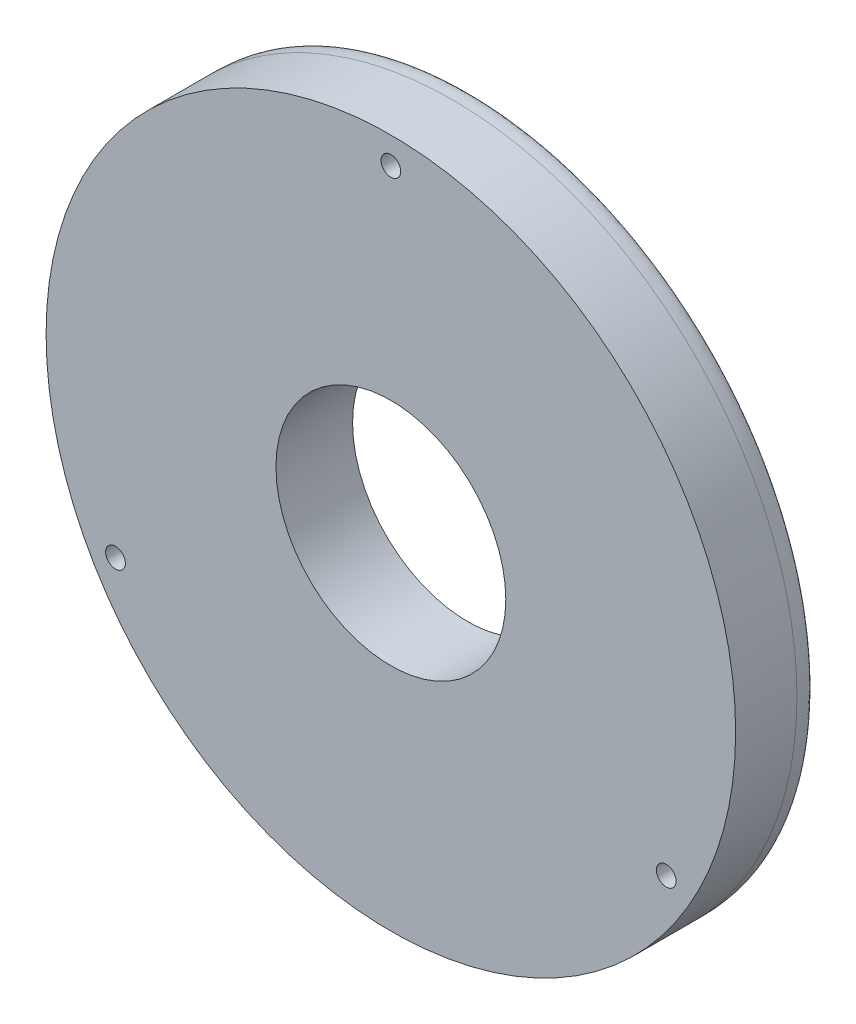
SolidWorks part; units mm, degrees
material "AISI 1020"
ref_plane "Front Plane" through (0, 0, 0) normal (0, 0, 1) x (1, 0, 0)
ref_plane "Top Plane" through (0, 0, 0) normal (0, 1, 0) x (1, 0, 0)
ref_plane "Right Plane" through (0, 0, 0) normal (1, 0, 0) x (0, 0, -1)
sketch "Sketch1" plane through (0, 0, 0) normal (0, 0, 1) x (1, 0, 0)
  line L0 (0, 96.52) -> (0, 114.3) construction
  circle A0 centre (0, 0) radius 114.3
  circle A1 centre (0, 0) radius 96.52 construction
  circle A2 centre (0, 0) radius 38.1
  point P7 (0, 105.41)
  dimension "D1" = 228.6
  dimension "D2" = 17.78
  dimension "D3" = 76.2
extrude "Boss-Extrude1" add sketch "Sketch1" along normal blind 25.4 contours A0 A2 region at (-111.0671, 0, 0)
hole_wizard "CBORE for 1/4 Socket Head Cap Screw1" positions "Sketch4" profile "Sketch5" counterbore size "1/4" standard "ANSI Inch"
sketch "Sketch4" plane through (0, 0, 0) normal (0, 0, -1) x (-1, 0, 0)
  point P0 (0, 105.41)
sketch "Sketch5" plane through (0, 105.41, 0) normal (1, 0, 0) x (0, 1, 0)
  line L0 (0, 0) -> (0, 27.3611)
  line L1 (0, 27.3611) -> (3.2639, 25.4)
  line L2 (3.2639, 25.4) -> (3.2639, 6.35)
  line L3 (3.2639, 6.35) -> (5.5562, 6.35)
  line L4 (5.5562, 6.35) -> (5.5562, 0)
  line L5 (5.5562, 0) -> (0, 0)
  line L10 (0, 27.3611) -> (-3.2639, 25.4) construction
  line L11 (0, -6.35) -> (0, 107.95) construction
  dimension "Hole Dia." = 6.5278
  dimension "Hole Depth" = 25.4
  dimension "C'Bore Dia." = 11.1125
  dimension "C'Bore Depth" = 6.35
  dimension "Drill Angle" = 118
pattern_circular "CirPattern1" count 3 over 360 about axis through (0, 0, 25.4) along (0, 0, 1) of "CBORE for 1/4 Socket Head Cap Screw1"
fillet "Fillet1" radius 1.27 1 edges at (114.3, 0, 0) second distance 5.08 conic rho 0.65 first distance on face at (85.7315, -52.705, 0)
